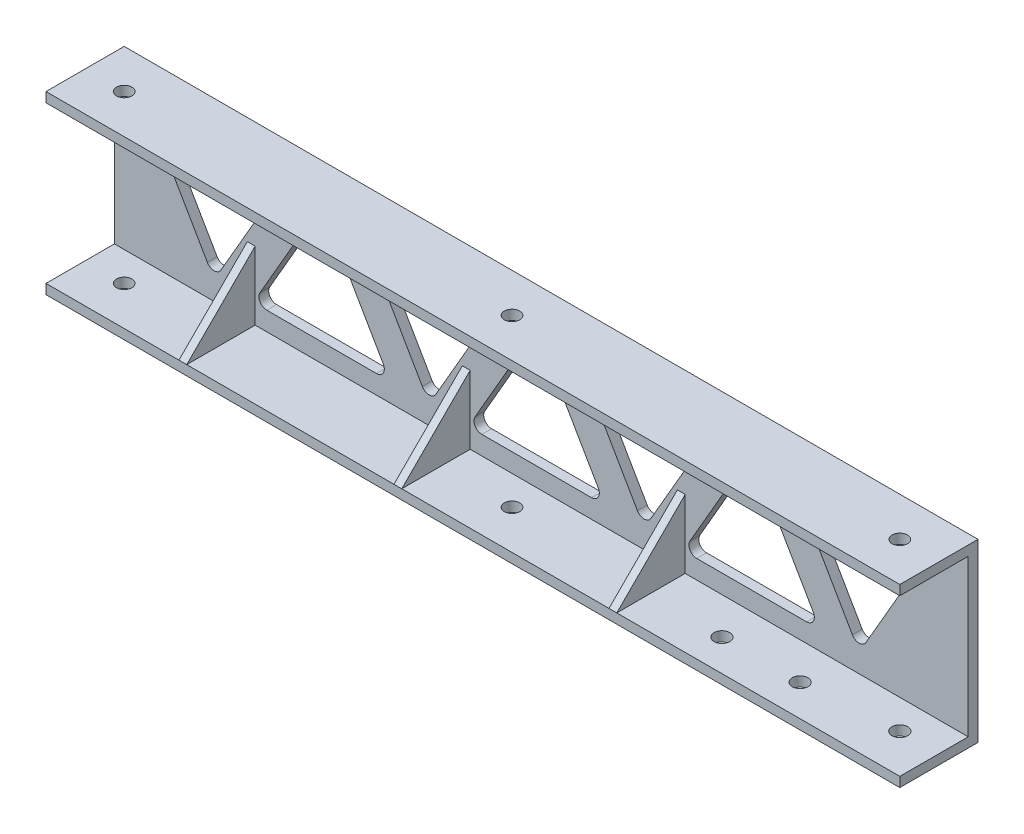
SolidWorks part; units mm, degrees
material "ABS PC"
ref_plane "Front Plane" through (0, 0, 0) normal (0, 0, 1) x (1, 0, 0)
ref_plane "Top Plane" through (0, 0, 0) normal (0, 1, 0) x (1, 0, 0)
ref_plane "Right Plane" through (0, 0, 0) normal (1, 0, 0) x (0, 0, -1)
sketch "Sketch1" plane through (0, 0, 0) normal (0, 0, 1) x (1, 0, 0)
  line L1 (277.368, 0) -> (277.368, 57.15)
  line L2 (277.368, 57.15) -> (0, 57.15)
  line L3 (0, 57.15) -> (0, 0)
  line L4 (0, 0) -> (277.368, 0)
  line L5 (30.1853, 13.081) -> (12.3597, 43.9558)
  line L6 (14.5594, 47.7658) -> (50.2106, 47.7658)
  line L7 (52.4103, 43.9558) -> (34.5847, 13.081)
  line L8 (32.385, 9.271) -> (45.085, 9.271) construction
  line L9 (49.4844, 9.271) -> (85.1356, 9.271)
  line L10 (87.3353, 13.081) -> (69.5097, 43.9558)
  line L11 (65.1103, 43.9558) -> (47.2847, 13.081)
  line L12 (100.0353, 13.081) -> (82.2097, 43.9558)
  line L13 (84.4094, 47.7658) -> (120.0606, 47.7658)
  line L14 (122.2603, 43.9558) -> (104.4347, 13.081)
  line L15 (102.235, 9.271) -> (114.935, 9.271) construction
  line L16 (119.3344, 9.271) -> (154.9856, 9.271)
  line L17 (157.1853, 13.081) -> (139.3597, 43.9558)
  line L18 (134.9603, 43.9558) -> (117.1347, 13.081)
  line L19 (169.8853, 13.081) -> (152.0597, 43.9558)
  line L20 (154.2594, 47.7658) -> (189.9106, 47.7658)
  line L21 (192.1103, 43.9558) -> (174.2847, 13.081)
  line L22 (172.085, 9.271) -> (184.785, 9.271) construction
  line L23 (189.1844, 9.271) -> (224.8356, 9.271)
  line L24 (227.0353, 13.081) -> (209.2097, 43.9558)
  line L25 (204.8103, 43.9558) -> (186.9847, 13.081)
  line L26 (239.7353, 13.081) -> (221.9097, 43.9558)
  line L27 (224.1094, 47.7658) -> (259.7606, 47.7658)
  line L28 (261.9603, 43.9558) -> (244.1347, 13.081)
  line L29 (241.935, 9.271) -> (252.095, 9.271) construction
  arc A0 (259.7606, 47.7658) -> (261.9603, 43.9558) centre (259.7606, 45.2258) cw
  arc A1 (221.9097, 43.9558) -> (224.1094, 47.7658) centre (224.1094, 45.2258) cw
  arc A2 (239.7353, 13.081) -> (244.1347, 13.081) centre (241.935, 14.351) ccw
  arc A3 (189.1844, 9.271) -> (186.9847, 13.081) centre (189.1844, 11.811) cw
  arc A4 (224.8356, 9.271) -> (227.0353, 13.081) centre (224.8356, 11.811) ccw
  arc A5 (209.2097, 43.9558) -> (204.8103, 43.9558) centre (207.01, 42.6858) ccw
  arc A6 (189.9106, 47.7658) -> (192.1103, 43.9558) centre (189.9106, 45.2258) cw
  arc A7 (152.0597, 43.9558) -> (154.2594, 47.7658) centre (154.2594, 45.2258) cw
  arc A8 (169.8853, 13.081) -> (174.2847, 13.081) centre (172.085, 14.351) ccw
  arc A9 (154.9856, 9.271) -> (157.1853, 13.081) centre (154.9856, 11.811) ccw
  arc A10 (119.3344, 9.271) -> (117.1347, 13.081) centre (119.3344, 11.811) cw
  arc A11 (139.3597, 43.9558) -> (134.9603, 43.9558) centre (137.16, 42.6858) ccw
  arc A12 (120.0606, 47.7658) -> (122.2603, 43.9558) centre (120.0606, 45.2258) cw
  arc A13 (82.2097, 43.9558) -> (84.4094, 47.7658) centre (84.4094, 45.2258) cw
  arc A14 (100.0353, 13.081) -> (104.4347, 13.081) centre (102.235, 14.351) ccw
  arc A15 (47.2847, 13.081) -> (49.4844, 9.271) centre (49.4844, 11.811) ccw
  arc A16 (69.5097, 43.9558) -> (65.1103, 43.9558) centre (67.31, 42.6858) ccw
  arc A17 (85.1356, 9.271) -> (87.3353, 13.081) centre (85.1356, 11.811) ccw
  arc A18 (34.5847, 13.081) -> (30.1853, 13.081) centre (32.385, 14.351) cw
  arc A19 (50.2106, 47.7658) -> (52.4103, 43.9558) centre (50.2106, 45.2258) cw
  arc A20 (12.3597, 43.9558) -> (14.5594, 47.7658) centre (14.5594, 45.2258) cw
  point P30 (264.16, 47.7658)
  point P33 (219.71, 47.7658)
  point P42 (229.235, 9.271)
  point P45 (207.01, 47.7658)
  point P48 (194.31, 47.7658)
  point P51 (149.86, 47.7658)
  point P57 (159.385, 9.271)
  point P63 (137.16, 47.7658)
  point P66 (124.46, 47.7658)
  point P69 (80.01, 47.7658)
  point P78 (67.31, 47.7658)
  point P81 (89.535, 9.271)
  point P87 (54.61, 47.7658)
  point P90 (10.16, 47.7658)
  dimension "D35" = 2.54
  dimension "D1" = 44.45
  dimension "D2" = 44.45
  dimension "D3" = 44.45
  dimension "D4" = 10.16
  dimension "D5" = 9.271
  dimension "D6" = 57.15
  dimension "D7" = 44.45
  dimension "D8" = 44.45
  dimension "D9" = 44.45
  dimension "D10" = 12.7
  dimension "D11" = 277.368
  dimension "D12" = 44.45
  dimension "D13" = 44.45
  dimension "D14" = 44.45
  dimension "D15" = 44.45
  dimension "D16" = 44.45
  dimension "D17" = 12.7
  dimension "D18" = 44.45
  dimension "D19" = 44.45
  dimension "D20" = 44.45
  dimension "D21" = 44.45
  dimension "D22" = 44.45
  dimension "D23" = 12.7
  dimension "D24" = 9.271
  dimension "D25" = 12.7
  dimension "D26" = 9.271
  dimension "D27" = 12.7
  dimension "D28" = 44.45
  dimension "D29" = 44.45
  dimension "D30" = 10.16
  dimension "D31" = 9.271
  dimension "D32" = 12.7
  dimension "D33" = 44.45
  dimension "D34" = 44.45
  dimension "D36" = 44.45
extrude "Boss-Extrude1" add sketch "Sketch1" along normal blind 3.175
sketch "Sketch2" plane through (0, 57.15, 0) normal (0, 1, 0) x (1, 0, 0)
  line L0 (0, 0) -> (0, -25.4)
  line L1 (0, -25.4) -> (277.368, -25.4)
  line L2 (277.368, -25.4) -> (277.368, 0)
  line L3 (277.368, 0) -> (0, 0)
  dimension "D1" = 25.4
extrude "Boss-Extrude2" add sketch "Sketch2" against normal blind 3.175
sketch "Sketch3" plane through (0, 0, 0) normal (0, -1, 0) x (1, 0, 0)
  line L0 (0, 0) -> (0, 25.4)
  line L1 (0, 25.4) -> (277.368, 25.4)
  line L2 (277.368, 25.4) -> (277.368, 0)
  line L3 (277.368, 0) -> (0, 0)
extrude "Boss-Extrude3" add sketch "Sketch3" against normal blind 3.175
sketch "Sketch4" plane through (0, 0, 3.175) normal (0, 0, 1) x (1, 0, 0)
  line L0 (0, 3.175) -> (277.368, 3.175) construction
  line L1 (0, 3.175) -> (43.18, 3.175) construction
  line L2 (43.18, 3.175) -> (113.03, 3.175) construction
  line L3 (113.03, 3.175) -> (182.88, 3.175) construction
  line L4 (277.368, 53.975) -> (0, 53.975) construction
  line L5 (0, 53.975) -> (76.708, 53.975) construction
  line L6 (76.708, 53.975) -> (146.558, 53.975) construction
  line L7 (146.558, 53.975) -> (216.408, 53.975) construction
  line L8 (43.18, 3.175) -> (43.18, 20.447) construction
  line L9 (113.03, 3.175) -> (113.03, 20.447) construction
  line L10 (182.88, 3.175) -> (182.88, 20.447) construction
  line L11 (216.408, 53.975) -> (216.408, 36.703) construction
  line L12 (146.558, 53.975) -> (146.558, 36.703) construction
  line L13 (76.708, 53.975) -> (76.708, 36.703) construction
  line L14 (277.368, 3.175) -> (277.368, 53.975) construction
  line L15 (0, 53.975) -> (0, 3.175) construction
  point P24 (113.03, 11.811)
  dimension "D1" = 69.85
  dimension "D2" = 69.85
  dimension "D3" = 60.96
  dimension "D4" = 43.18
  dimension "D5" = 69.85
  dimension "D6" = 69.85
ref_plane "Plane1" through (43.18, 0, 0) normal (1, 0, 0) x (0, 1, 0)
ref_plane "Plane2" through (113.03, 0, 0) normal (1, 0, 0) x (0, 1, 0)
ref_plane "Plane3" through (182.88, 0, 0) normal (1, 0, 0) x (0, 1, 0)
ref_plane "Plane4" through (216.408, 0, 0) normal (-1, 0, 0) x (0, -1, 0)
ref_plane "Plane5" through (146.558, 0, 0) normal (-1, 0, 0) x (0, -1, 0)
ref_plane "Plane6" through (76.708, 0, 0) normal (-1, 0, 0) x (0, -1, 0)
sketch "Sketch5" plane through (43.18, 0, 0) normal (1, 0, 0) x (0, 1, 0)
  line L0 (3.175, 3.175) -> (3.175, 25.4)
  line L1 (3.175, 3.175) -> (25.4, 3.175)
  line L2 (3.175, 3.175) -> (53.975, 3.175) construction
  line L3 (25.4, 3.175) -> (3.175, 25.4)
  dimension "D1" = 22.225
  dimension "D2" = 22.225
extrude "Boss-Extrude4" add sketch "Sketch5" along normal blind 2.54
sketch "Sketch6" plane through (113.03, 0, 0) normal (1, 0, 0) x (0, 1, 0)
  line L0 (3.175, 25.4) -> (3.175, 3.175)
  line L1 (3.175, 3.175) -> (25.4, 3.175)
  line L2 (25.4, 3.175) -> (3.175, 25.4)
extrude "Boss-Extrude5" add sketch "Sketch6" along normal blind 2.54
sketch "Sketch7" plane through (182.88, 0, 0) normal (1, 0, 0) x (0, 1, 0)
  line L0 (3.175, 25.4) -> (3.175, 3.175)
  line L1 (3.175, 3.175) -> (25.4, 3.175)
  line L2 (25.4, 3.175) -> (3.175, 25.4)
extrude "Boss-Extrude6" add sketch "Sketch7" along normal blind 2.54
sketch "Sketch8" plane through (76.708, 0, 0) normal (-1, 0, 0) x (0, -1, 0)
  line L0 (-53.975, 3.175) -> (-53.975, 25.4)
  line L1 (-53.975, 25.4) -> (-31.75, 3.175)
  line L2 (-3.175, 3.175) -> (-53.975, 3.175) construction
  line L3 (-31.75, 3.175) -> (-53.975, 3.175)
extrude "Boss-Extrude7" add sketch "Sketch8" against normal blind 2.54
sketch "Sketch9" plane through (146.558, 0, 0) normal (-1, 0, 0) x (0, -1, 0)
  line L0 (-53.975, 25.4) -> (-53.975, 3.175)
  line L1 (-53.975, 3.175) -> (-31.75, 3.175)
  line L2 (-31.75, 3.175) -> (-53.975, 25.4)
extrude "Boss-Extrude8" add sketch "Sketch9" against normal blind 2.54
sketch "Sketch10" plane through (216.408, 0, 0) normal (-1, 0, 0) x (0, -1, 0)
  line L0 (-53.975, 25.4) -> (-53.975, 3.175)
  line L1 (-53.975, 3.175) -> (-31.75, 3.175)
  line L2 (-31.75, 3.175) -> (-53.975, 25.4)
extrude "Boss-Extrude9" add sketch "Sketch10" against normal blind 2.54
hole_wizard "#10 Clearance Hole1" positions "Sketch11" profile "Sketch12" hole size "#10" standard "ANSI Inch" end condition through all
sketch "Sketch11" plane through (0, 3.175, 0) normal (0, 1, 0) x (1, 0, 0)
  point P0 (209.2997, -15.125)
  point P3 (234.6997, -15.125)
sketch "Sketch12" plane through (209.2997, 3.175, 15.125) normal (1, 0, 0) x (0, 0, 1)
  line L0 (0, 0) -> (0, 3.175)
  line L1 (0, 3.175) -> (2.5527, 3.175)
  line L2 (2.5527, 3.175) -> (2.5527, 0)
  line L5 (2.5527, 0) -> (0, 0)
  line L11 (0, -6.35) -> (0, 107.95) construction
  dimension "Thru Hole Dia." = 5.1054
  dimension "Thru Hole Depth" = 3.175
hole_wizard "#10 Clearance Hole2" positions "Sketch17" profile "Sketch16" hole size "#10" standard "ANSI Inch" end condition through all
sketch "Sketch17" plane through (0, 3.175, 0) normal (0, 1, 0) x (1, 0, 0)
  point P0 (264.668, -12.7)
sketch "Sketch16" plane through (264.668, 3.175, 12.7) normal (1, 0, 0) x (0, 0, 1)
  line L0 (0, 0) -> (0, 3.175)
  line L1 (0, 3.175) -> (2.5527, 3.175)
  line L2 (2.5527, 3.175) -> (2.5527, 0)
  line L5 (2.5527, 0) -> (0, 0)
  line L11 (0, -6.35) -> (0, 107.95) construction
  dimension "Thru Hole Dia." = 5.1054
  dimension "Thru Hole Depth" = 3.175
hole_wizard "#10 Clearance Hole3" positions "Sketch18" profile "Sketch19" hole size "#10" standard "ANSI Inch" end condition through all
sketch "Sketch18" plane through (0, 3.175, 0) normal (0, 1, 0) x (1, 0, 0)
  point P0 (138.684, -12.7)
  point P3 (264.668, -12.7)
  point P6 (12.7, -12.7)
sketch "Sketch19" plane through (138.684, 3.175, 12.7) normal (1, 0, 0) x (0, 0, 1)
  line L0 (0, 0) -> (0, 3.175)
  line L1 (0, 3.175) -> (2.4892, 3.175)
  line L2 (2.4892, 3.175) -> (2.4892, 0)
  line L5 (2.4892, 0) -> (0, 0)
  line L11 (0, -6.35) -> (0, 107.95) construction
  dimension "Thru Hole Dia." = 4.9784
  dimension "Thru Hole Depth" = 3.175
hole_wizard "#10 Clearance Hole4" positions "Sketch20" profile "Sketch21" hole size "#10" standard "ANSI Inch" end condition through all
sketch "Sketch20" plane through (0, 53.975, 0) normal (0, -1, 0) x (-1, 0, 0)
  point P0 (-138.684, -12.7)
  point P3 (-264.668, -12.7)
  point P6 (-12.7, -12.7)
sketch "Sketch21" plane through (138.684, 53.975, 12.7) normal (1, 0, 0) x (0, 0, -1)
  line L0 (0, 0) -> (0, 3.175)
  line L1 (0, 3.175) -> (2.4892, 3.175)
  line L2 (2.4892, 3.175) -> (2.4892, 0)
  line L5 (2.4892, 0) -> (0, 0)
  line L11 (0, -6.35) -> (0, 107.95) construction
  dimension "Thru Hole Dia." = 4.9784
  dimension "Thru Hole Depth" = 3.175
